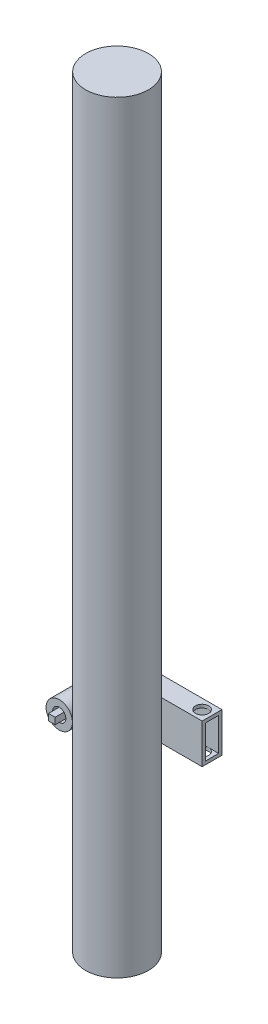
SolidWorks part; units mm, degrees
ref_plane "Front Plane" through (0, 0, 0) normal (0, 0, 1) x (1, 0, 0)
ref_plane "Top Plane" through (0, 0, 0) normal (0, 1, 0) x (1, 0, 0)
ref_plane "Right Plane" through (0, 0, 0) normal (1, 0, 0) x (0, 0, -1)
sketch "Elevation Bar" plane through (0, 0, 0) normal (0, 1, 0) x (1, 0, 0)
  circle A0 centre (0, 0) radius 30.226
  dimension "D1" = 60.452
extrude "Elevation Bar Part" add sketch "Elevation Bar" along normal blind 734.06
sketch "Pole and Drivetrain Pos" plane through (0, 0, 0) normal (0, 0, 1) x (1, 0, 0)
  line L0 (0, 0) -> (172.1794, 0) construction
  line L1 (-30.226, 0) -> (-30.226, 734.06) construction
  line L2 (-30.226, 734.06) -> (30.226, 734.06) construction
  line L3 (30.226, 734.06) -> (30.226, 0) construction
  line L4 (30.226, 0) -> (30.226, 734.06) construction
  line L5 (636.651, 40.7185) -> (27.051, 40.7185) construction
  line L6 (636.651, 53.4185) -> (27.051, 53.4185)
  line L7 (636.651, 53.4185) -> (636.651, 28.0185)
  line L8 (636.651, 28.0185) -> (27.051, 28.0185)
  line L9 (27.051, 53.4185) -> (27.051, 28.0185)
  line L10 (-30.226, 93.98) -> (30.226, 93.98) construction
  line L11 (33.2486, 0) -> (-33.2486, 0) construction
  line L12 (30.226, 185.42) -> (-30.226, 185.42) construction
  line L13 (30.226, 276.86) -> (-30.226, 276.86) construction
  line L14 (30.226, 368.3) -> (-30.226, 368.3) construction
  line L15 (30.226, 459.74) -> (-30.226, 459.74) construction
  line L16 (30.226, 551.18) -> (-30.226, 551.18) construction
  line L17 (30.226, 642.62) -> (-30.226, 642.62) construction
  line L18 (30.226, 73.152) -> (750.8896, 73.152) construction
  circle A0 centre (576.5632, 40.7185) radius 41.275 construction
  circle A1 centre (87.1388, 40.7185) radius 41.275 construction
  circle A2 centre (331.851, 40.7185) radius 41.275 construction
  point P24 (331.851, 40.7185)
  dimension "D2" = 82.55
  dimension "D1" = 609.6
  dimension "D3" = 25.4
  dimension "D4" = 244.7122
  dimension "D5" = 244.7122
  dimension "D6" = 93.98
  dimension "D7" = 185.42
  dimension "D8" = 276.86
  dimension "D9" = 368.3
  dimension "D10" = 459.74
  dimension "D11" = 551.18
  dimension "D12" = 642.62
  dimension "D13" = 73.152
sketch "Driving Wheels Geo" plane through (0, 0, 0) normal (0, 0, 1) x (1, 0, 0)
  line L0 (-30.226, 182.88) -> (-30.226, 101.727) construction
  line L1 (55.626, 101.727) -> (30.226, 101.727) construction
  line L2 (-30.226, 0) -> (-30.226, 734.06) construction
  line L3 (30.226, 734.06) -> (30.226, 0) construction
  line L5 (30.226, 101.727) -> (-30.226, 101.727) construction
  line L6 (-30.226, 182.88) -> (30.226, 101.727) construction
  line L7 (31.8135, 101.727) -> (-30.226, 182.88) construction
  line L8 (30.226, 226.8605) -> (203.668, 53.4185) construction
  line L9 (-42.926, 195.58) -> (44.3164, 195.58) construction
  line L10 (30.226, 73.152) -> (750.8896, 73.152) construction
  line L11 (636.651, 53.4185) -> (27.051, 53.4185) construction
  line L14 (-42.926, 170.18) -> (44.3164, 170.18) construction
  line L15 (44.3164, 170.18) -> (44.3164, 195.58) construction
  line L17 (31.6164, 195.58) -> (57.0164, 195.58) construction
  line L18 (31.6164, 195.58) -> (31.6164, 170.18) construction
  line L19 (31.6164, 170.18) -> (57.0164, 170.18) construction
  line L20 (57.0164, 195.58) -> (57.0164, 170.18) construction
  line L21 (31.6164, 195.58) -> (57.0164, 170.18) construction
  line L22 (31.6164, 170.18) -> (57.0164, 195.58) construction
  circle A1 centre (55.626, 101.727) radius 25.4
  circle A3 centre (-42.926, 182.88) radius 12.7
  circle A4 centre (81.026, 104.2185) radius 50.8 construction
  circle A5 centre (55.626, 101.727) radius 23.8125 construction
  point P28 (44.3164, 182.88)
  dimension "D1" = 50.8
  dimension "D2" = 1.5875
  dimension "D3" = 52.603
  dimension "D4" = 3.175
  dimension "D5" = 182.88
  dimension "D8" = 101.6
  dimension "D6" = 25.4
  dimension "D13" = 3.175
  dimension "D7" = 81.153
  dimension "D9" = 45
  dimension "D10" = 53.317
  dimension "D11" = 25.4
  dimension "D12" = 48.3085
ref_plane "Plane1" through (0, 182.88, 0) normal (0, 1, 0) x (1, 0, 0)
sketch "Clamp Geo" plane through (0, 182.88, 0) normal (0, 1, 0) x (1, 0, 0)
  line L0 (-42.926, -19.8438) -> (-42.926, 50.8635) construction
  line L3 (27.051, 228.6) -> (27.051, -228.6) construction
  line L4 (50.0464, 31.8135) -> (-49.276, 31.8135)
  line L5 (50.0464, 31.8135) -> (50.0464, 50.8635)
  line L6 (50.0464, 50.8635) -> (-49.276, 50.8635)
  line L7 (-49.276, 31.8135) -> (-49.276, 50.8635)
  line L10 (-46.101, 50.8635) -> (-39.751, 50.8635)
  line L11 (-46.101, 50.8635) -> (-46.101, -19.8438)
  line L12 (-46.101, -19.8438) -> (-39.751, -19.8438)
  line L13 (-39.751, 50.8635) -> (-39.751, -19.8438)
  line L14 (-55.626, 12.7) -> (-30.226, 12.7) construction
  line L15 (-55.626, 12.7) -> (-55.626, -12.7) construction
  line L16 (-55.626, -12.7) -> (-30.226, -12.7) construction
  line L17 (-30.226, 12.7) -> (-30.226, -12.7) construction
  line L18 (-55.626, 12.7) -> (-30.226, -12.7) construction
  line L19 (-55.626, -12.7) -> (-30.226, 12.7) construction
  line L20 (0, -30.226) -> (0, 30.226) construction
  line L21 (-30.226, 0) -> (30.226, 0) construction
  line L22 (-46.101, 46.101) -> (-42.926, 46.101) construction
  line L23 (-39.751, 41.3385) -> (-46.101, 41.3385)
  line L24 (-46.101, 41.3385) -> (-46.101, 50.8635) construction
  line L25 (-39.751, 31.8135) -> (-39.751, 50.8635) construction
  line L26 (50.0464, 41.3385) -> (40.5214, 41.3385) construction
  circle A0 centre (0, 0) radius 30.226 construction
  circle A3 centre (-42.926, 46.101) radius 1.8288
  circle A5 centre (-42.926, 36.576) radius 1.8288
  circle A6 centre (40.5214, 41.3385) radius 6.35
  circle A7 centre (40.5214, 41.3385) radius 13.4704 construction
  point P14 (-42.926, 0)
  point P32 (-39.751, 41.3385)
  point P34 (-46.101, 41.3385)
  point P36 (-42.926, 41.3385)
  point P42 (50.0464, 41.3385)
  dimension "D1" = 60.452
  dimension "D4" = 1.5875
  dimension "D7" = 3.6576
  dimension "D8" = 3.175
  dimension "D10" = 12.7
  dimension "D11" = 3.175
  dimension "D2" = 457.2
  dimension "D3" = 19.05
  dimension "D5" = 6.35
  dimension "D6" = 25.4
  dimension "D9" = 99.3224
  dimension "D13" = 7.1437
sketch "Locked Setting Geo" plane through (0, 182.88, 0) normal (0, 1, 0) x (1, 0, 0)
  line L0 (30.2525, 144.301) -> (91.1428, 108.3583) construction
  line L1 (27.477, 37.9778) -> (77.9656, 123.5104)
  line L2 (27.477, 37.9778) -> (43.8821, 28.2941)
  line L3 (43.8821, 28.2941) -> (94.3707, 113.8267)
  line L4 (77.9656, 123.5104) -> (94.3707, 113.8267)
  line L5 (92.7568, 111.0925) -> (89.5289, 105.6242)
  line L6 (92.7568, 111.0925) -> (31.8664, 147.0352)
  line L7 (31.8664, 147.0352) -> (28.6385, 141.5668)
  line L8 (89.5289, 105.6242) -> (28.6385, 141.5668)
  line L9 (64.7337, 138.6948) -> (51.8221, 116.8213) construction
  line L10 (64.7337, 138.6948) -> (42.8602, 151.6064) construction
  line L11 (42.8602, 151.6064) -> (29.9486, 129.7329) construction
  line L12 (51.8221, 116.8213) -> (29.9486, 129.7329) construction
  line L13 (64.7337, 138.6948) -> (29.9486, 129.7329) construction
  line L14 (42.8602, 151.6064) -> (51.8221, 116.8213) construction
  line L17 (88.6555, 113.5135) -> (87.0416, 110.7793) construction
  line L18 (81.3263, 110.466) -> (84.5542, 115.9344)
  line L19 (84.5542, 115.9344) -> (92.7568, 111.0925) construction
  line L20 (73.1238, 115.3079) -> (89.5289, 105.6242) construction
  line L21 (35.6795, 33.1359) -> (40.5214, 41.3385) construction
  line L22 (50.0464, 50.8635) -> (-49.276, 50.8635) construction
  line L23 (-46.101, 50.8635) -> (-46.101, -19.8438) construction
  line L24 (27.051, 228.6) -> (27.051, -228.6) construction
  circle A1 centre (87.0416, 110.7793) radius 1.8288
  circle A2 centre (78.839, 115.6211) radius 1.8288
  circle A3 centre (40.5214, 41.3385) radius 6.35
  point P10 (47.3411, 134.2138)
  point P28 (81.3263, 110.466)
  point P30 (84.5542, 115.9344)
  point P32 (82.9403, 113.2002)
  point P36 (35.6795, 33.1359)
  point P40 (40.5214, 41.3385)
  point P44 (-17.1792, 28.8062)
  dimension "D6" = 3.6576
  dimension "D9" = 12.7
  dimension "D2" = 19.05
  dimension "D3" = 1.5875
  dimension "D4" = 6.35
  dimension "D5" = 25.4
  dimension "D7" = 3.175
  dimension "D8" = 99.3224
  dimension "D10" = 3.175
  dimension "D11" = 50.8635
  dimension "D12" = 67.3197
extrude "Boss-Extrude1" add sketch "Clamp Geo" along normal blind 19.05 and the other way blind 19.05 separate body contours L6 L13 L4 L5 A6 | L11 L6 L7 L4 | L13 L23 L11 L4 A5 | L23 L13 L6 L11 A3 region at (2.3187, 182.88, -41.3385) region at (-42.926, 182.88, -31.928) region at (-47.6885, 182.88, -41.3385) region at (-42.926, 182.88, -41.453)
sketch "Sketch2" plane through (-49.276, 0, 0) normal (-1, 0, 0) x (0, 0, 1)
  line L0 (-41.3385, 201.93) -> (-41.3385, 163.83) construction
  line L1 (-31.8135, 201.93) -> (-50.8635, 201.93) construction
  line L2 (-31.8135, 163.83) -> (-50.8635, 163.83) construction
  line L3 (-31.8135, 163.83) -> (-31.8135, 201.93) construction
  line L4 (-47.6885, 167.005) -> (-34.9885, 167.005)
  line L5 (-47.6885, 167.005) -> (-47.6885, 198.755)
  line L6 (-47.6885, 198.755) -> (-34.9885, 198.755)
  line L7 (-34.9885, 167.005) -> (-34.9885, 198.755)
  line L8 (-47.6885, 167.005) -> (-34.9885, 198.755) construction
  line L9 (-47.6885, 198.755) -> (-34.9885, 167.005) construction
  point P6 (-41.3385, 182.88)
  dimension "D1" = 3.175
  dimension "D2" = 3.175
extrude "Cut-Extrude2" cut sketch "Sketch2" against normal up to surface (99.3224 mm away) up to face at (50.0464, 182.88, -41.3385)
sketch "Sketch3" plane through (0, 0, -50.8635) normal (0, 0, -1) x (-1, 0, 0)
  line L2 (39.7129, 179.6669) -> (46.1391, 179.6669)
  line L3 (39.7129, 179.6669) -> (39.7129, 186.0931)
  line L4 (39.7129, 186.0931) -> (46.1391, 186.0931)
  line L5 (46.1391, 179.6669) -> (46.1391, 186.0931)
  line L6 (39.7129, 179.6669) -> (46.1391, 186.0931) construction
  line L7 (39.7129, 186.0931) -> (46.1391, 179.6669) construction
  point P0 (42.926, 182.88)
  point P1 (42.926, 182.88)
  dimension "D1" = 6.4262
extrude "Cut-Extrude3" cut sketch "Sketch3" against normal up to surface (19.05 mm away) up to face at (0.3852, 182.88, -31.8135)
extrude "Boss-Extrude2" add sketch "Clamp Geo<3>" along normal blind 3.175 and the other way blind 3.175 separate body contours L13 L4 L11 L12 | L13 L23 L11 L4 A5 | L23 L13 L6 L11 A3 region at (-42.926, 182.88, -5.9849) region at (-42.926, 182.88, -31.928) region at (-42.926, 182.88, -41.453)
sketch "Clamp Geo<3>" plane through (0, 182.88, 0) normal (0, 1, 0) x (1, 0, 0) same geometry as "Clamp Geo"
sketch "Custom Driven Flywheel" plane through (0, 0, 0) normal (0, 0, 1) x (1, 0, 0)
  circle A0 centre (-42.926, 182.88) radius 12.7 construction
  circle A1 centre (-42.926, 182.88) radius 12.7
  circle A2 centre (-42.926, 182.88) radius 6.35
  dimension "D1" = 12.7
extrude "Boss-Extrude3" add sketch "Custom Driven Flywheel" along normal mid plane 25.4 separate body
equation "\"D5@Pole and Drivetrain Pos\" = \"D4@Pole and Drivetrain Pos\""
